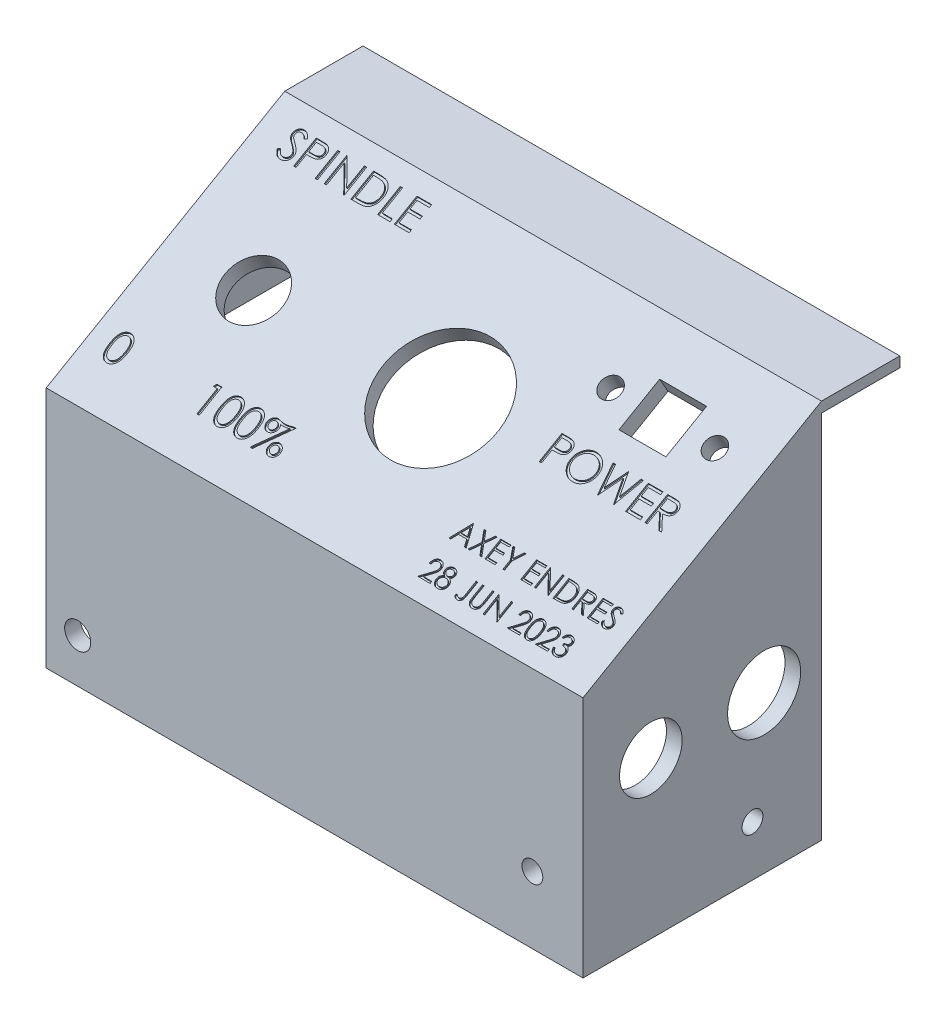
SolidWorks part; units mm, degrees
ref_plane "Front Plane" through (0, 0, 0) normal (0, 0, 1) x (1, 0, 0)
ref_plane "Top Plane" through (0, 0, 0) normal (0, 1, 0) x (1, 0, 0)
ref_plane "Right Plane" through (0, 0, 0) normal (1, 0, 0) x (0, 0, -1)
sketch "Sketch1" plane through (0, 0, 0) normal (0, 0, 1) x (1, 0, 0)
  line L1 (0, 0) -> (96.8908, 0)
  line L2 (0, 0) -> (0, 44.5172)
  line L3 (0, 44.5172) -> (96.8908, 44.5172)
  line L4 (96.8908, 0) -> (96.8908, 44.5172)
extrude "Boss-Extrude1" add sketch "Sketch1" along normal blind 3
sketch "Sketch2" plane through (96.8908, 0, 0) normal (1, 0, 0) x (0, 0, -1)
  line L7 (0, 0) -> (0, 44.5172)
  line L8 (0, 44.5172) -> (-3, 44.5172)
  line L9 (-3, 44.5172) -> (-3, 0)
  line L10 (-3, 0) -> (0, 0)
  line L11 (0, 0) -> (0, 44.5172)
  line L13 (-3, 44.5172) -> (-3, 0)
  line L14 (-3, 0) -> (0, 0)
  line L20 (0, 44.5172) -> (42.7172, 69.18)
  line L21 (-3, 44.5172) -> (-3, 46.5172)
  line L22 (-3, 46.5172) -> (31.3743, 66.3632)
  line L24 (31.3743, 66.3632) -> (42.7163, 72.9116)
  line L25 (42.7163, 72.9116) -> (42.7172, 69.18)
  dimension "D1" = 0
extrude "Boss-Extrude3" add sketch "Sketch2" against normal up to surface (96.8908 mm away) up to face at (0, 22.2586, 1.5)
sketch "Sketch3" plane through (96.8908, 0, 0) normal (1, 0, 0) x (0, 0, -1)
  line L0 (-3, 0) -> (42.7172, 0)
  line L1 (42.7172, 0) -> (42.7163, 72.9116)
  line L2 (42.7163, 72.9116) -> (-3, 46.5172)
  line L3 (-3, 46.5172) -> (-3, 0)
extrude "Boss-Extrude4" add sketch "Sketch3" along normal blind 3
sketch "Sketch4" plane through (0, 0, 0) normal (-1, 0, 0) x (0, 0, 1)
  line L0 (0, 44.5172) -> (3, 44.5172)
  line L1 (3, 46.5172) -> (3, 0) construction
  line L2 (0, 44.5172) -> (-42.7169, 44.5172)
  line L3 (-42.7172, 0) -> (-42.7167, 69.1799) construction
  line L4 (-42.7169, 44.5172) -> (-42.7163, 72.9116)
  line L5 (-42.7163, 72.9116) -> (3, 46.5172)
  line L6 (3, 46.5172) -> (3, 44.5172)
extrude "Boss-Extrude5" add sketch "Sketch4" along normal blind 3
sketch "Sketch6" plane through (0, 0, 0) normal (-1, 0, 0) x (0, 0, 1)
  line L1 (0, 44.5172) -> (3, 44.5172)
  line L2 (0, 44.5172) -> (0, 0)
  line L3 (0, 0) -> (3, 0)
  line L4 (3, 44.5172) -> (3, 0)
extrude "Boss-Extrude7" add sketch "Sketch6" along normal blind 3
sketch "Sketch7" plane through (-3, 0, 0) normal (-1, 0, 0) x (0, 0, 1)
  line L0 (0, 44.5172) -> (0, 39.5172)
  line L1 (0, 44.5172) -> (0, 0) construction
  line L2 (0, 39.5172) -> (-5, 44.5172)
  line L3 (-42.7169, 44.5172) -> (0, 44.5172) construction
  line L4 (-5, 44.5172) -> (0, 44.5172)
extrude "Boss-Extrude8" add sketch "Sketch7" against normal blind 3 separate body
sketch "Sketch9" plane through (96.8908, 0, 0) normal (-1, 0, 0) x (0, 0, 1)
  circle A0 centre (-29.4799, 9.672) radius 2
extrude "Cut-Extrude1" cut sketch "Sketch9" against normal blind 10
sketch "Sketch10" plane through (0, 0, 0) normal (0, 0, -1) x (-1, 0, 0)
  circle A0 centre (-90.1855, 12.8349) radius 2
  circle A1 centre (-3.0304, 8.4351) radius 2.5
extrude "Cut-Extrude2" cut sketch "Sketch10" against normal blind 10
sketch "Sketch11" plane through (99.8908, 0, 0) normal (1, 0, 0) x (0, 0, -1)
  circle A1 centre (10, 30) radius 6
  circle A3 centre (31.7169, 30) radius 7
  point P11 (-3, 30)
extrude "Cut-Extrude3" cut sketch "Sketch11" against normal blind 10
sketch "Sketch12" plane through (0, 36.187, 20.8926) normal (0, 0.866, 0.5) x (1, 0, 0)
  line L3 (76.3908, 55.7521) -> (85.3908, 55.7521)
  line L8 (76.3908, 55.7521) -> (76.3908, 64.7521)
  line L9 (76.3908, 64.7521) -> (85.3908, 64.7521)
  line L10 (85.3908, 55.7521) -> (85.3908, 64.7521)
  circle A0 centre (70.8908, 60.2521) radius 2
  circle A1 centre (90.8908, 60.2521) radius 2
  point P7 (80.8908, 60.2521)
  point P10 (80.8908, 60.2521)
extrude "Cut-Extrude5" cut sketch "Sketch12" against normal blind 10
sketch "Sketch13" plane through (0, 36.187, 20.8926) normal (0, 0.866, 0.5) x (1, 0, 0)
  circle A7 centre (13.8991, 47.0549) radius 5.5
  circle A10 centre (49.7267, 47.0549) radius 11
sketch "Sketch14" plane through (0, 36.187, 20.8926) normal (0, 0.866, 0.5) x (1, 0, 0)
  text T0 "POWER" font "Century Gothic" height 5
  text T1 "AXEY ENDRES\r\n28 JUN 2023"
extrude "Cut-Extrude7" cut sketch "Sketch14" against normal blind 0.3
extrude "Cut-Extrude8" cut sketch "Sketch13" against normal blind 20.3
sketch "Sketch15" plane through (0, 36.187, 20.8926) normal (0, 0.866, 0.5) x (1, 0, 0)
  text T0 "SPINDLE" font "Century Gothic" height 5
  text T1 "0       100%" font "Century Gothic" height 5
extrude "Cut-Extrude9" cut sketch "Sketch15" against normal blind 0.3
sketch "Sketch16" plane through (99.8908, 0, 0) normal (1, 0, 0) x (0, 0, -1)
  line L1 (42.7163, 72.9116) -> (57.7163, 72.9116)
  line L2 (42.7163, 72.9116) -> (42.7163, 70.9116)
  line L3 (42.7163, 70.9116) -> (57.7163, 70.9116)
  line L4 (57.7163, 72.9116) -> (57.7163, 70.9116)
extrude "Boss-Extrude9" add sketch "Sketch16" against normal up to surface (102.8908 mm away) up to face at (-3, 34.7439, -13.2389)
